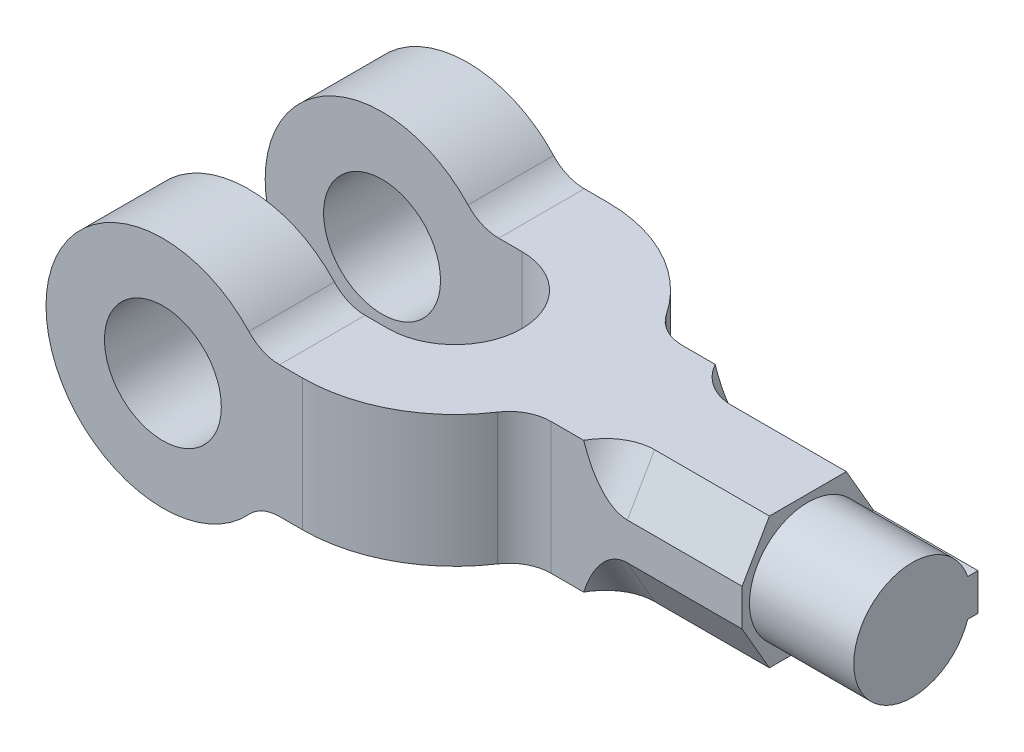
SolidWorks part; units mm, degrees
ref_plane "Front Plane" through (0, 0, 0) normal (0, 0, 1) x (1, 0, 0)
ref_plane "Top Plane" through (0, 0, 0) normal (0, 1, 0) x (1, 0, 0)
ref_plane "Right Plane" through (0, 0, 0) normal (1, 0, 0) x (0, 0, -1)
sketch "Sketch2" plane through (0, 0, 0) normal (0, 0, 1) x (1, 0, 0)
  circle A0 centre (0, 0) radius 28
  circle A1 centre (0, 0) radius 56
  dimension "D1" = 56
  dimension "D2" = 112
extrude "Boss-Extrude1" add sketch "Sketch2" along normal blind 41
ref_plane "Plane1" through (0, 0, -32) normal (0, 0, -1) x (-1, 0, 0)
mirror "Mirror4" about plane through (0, 0, -32) normal (0, 0, -1) of bodies 101
sketch "Sketch3" plane through (0, 0, 0) normal (0, 1, 0) x (1, 0, 0)
  line L0 (-0.029, 112.5865) -> (-0.029, -49887.4135) construction
  line L1 (1.2997, 32) -> (50001.2997, 32) construction
  line L3 (66.971, 32) -> (66.971, 50032) construction
  line L4 (56, 105) -> (-56, 105) construction
  line L5 (66.971, 105) -> (66.971, 64)
  line L6 (66.971, 0) -> (66.971, -41)
  arc A0 (66.971, 0) -> (66.971, 64) centre (66.971, 32) ccw
  arc A1 (66.971, -41) -> (66.971, 105) centre (66.971, 32) ccw
  dimension "D3" = 64
  dimension "D4" = 146
  dimension "D1" = 73
  dimension "D2" = 67
extrude "Boss-Extrude2" add sketch "Sketch3" along normal mid plane 63 separate body
sketch "Sketch4" plane through (66.971, 0, 0) normal (-1, 0, 0) x (0, 0, 1)
  line L0 (0, -31.5) -> (41, -31.5) construction
  line L1 (41, -31.5) -> (41, 31.5) construction
  line L2 (41, 31.5) -> (0, 31.5) construction
  line L3 (0, 31.5) -> (0, -31.5) construction
  line L4 (-105, -31.5) -> (-64, -31.5) construction
  line L5 (-64, -31.5) -> (-64, 31.5) construction
  line L6 (-64, 31.5) -> (-105, 31.5) construction
  line L7 (-105, 31.5) -> (-105, -31.5) construction
  line L8 (0, -31.5) -> (41, -31.5)
  line L9 (41, -31.5) -> (41, 31.5)
  line L10 (41, 31.5) -> (0, 31.5)
  line L11 (0, 31.5) -> (0, -31.5)
  line L12 (-105, -31.5) -> (-64, -31.5)
  line L13 (-64, -31.5) -> (-64, 31.5)
  line L14 (-64, 31.5) -> (-105, 31.5)
  line L15 (-105, 31.5) -> (-105, -31.5)
extrude "Boss-Extrude3" add sketch "Sketch4" along normal up to surface (20.6704 mm away) up to face at (56, 0, -105)
fillet "Fillet1" radius 20 4 edges at (46.3006, -31.5, 20.5) (46.3006, -31.5, -84.5) (46.3006, 31.5, 20.5) (46.3006, 31.5, -84.5)
ref_plane "Plane2" through (236, 0, 0) normal (1, 0, 0) x (0, 0, -1)
sketch "Sketch6" plane through (236, 0, 0) normal (1, 0, 0) x (0, 0, -1)
  line L0 (0, 0) -> (-50000, 0) construction
  line L1 (32, 0) -> (32, 50000) construction
  line L3 (105, 31.5) -> (105, -31.5) construction
  line L4 (105, 31.5) -> (-41, 31.5) construction
  line L5 (63.5, -31.5) -> (0.5, -31.5)
  line L6 (63.5, -31.5) -> (63.5, 31.5)
  line L7 (63.5, 31.5) -> (0.5, 31.5)
  line L8 (0.5, -31.5) -> (0.5, 31.5)
  line L9 (63.5, -31.5) -> (0.5, 31.5) construction
  line L10 (63.5, 31.5) -> (0.5, -31.5) construction
  point P7 (32, 0)
  dimension "D1" = 73
  dimension "D2" = 63
extrude "Boss-Extrude4" add sketch "Sketch6" against normal up to next
fillet "Fillet2" radius 20 2 edges at (132.825, 0, -0.5) (132.825, 0, -63.5)
sketch "Sketch7" plane through (236, 0, 0) normal (1, 0, 0) x (0, 0, -1)
  line L0 (32, -61.6) -> (32, 61.6) construction
  circle A0 centre (32, 0) radius 28
  dimension "D1" = 56
extrude "Boss-Extrude5" add sketch "Sketch7" along normal blind 50
sketch "Sketch8" plane through (236, 0, 0) normal (1, 0, 0) x (0, 0, -1)
  line L1 (68.6181, 0) -> (50.3091, 31.7122)
  line L2 (50.3091, 31.7122) -> (13.6909, 31.7122)
  line L3 (13.6909, 31.7122) -> (-4.6181, 0)
  line L4 (-4.6181, 0) -> (13.6909, -31.7122)
  line L5 (13.6909, -31.7122) -> (50.3091, -31.7122)
  line L6 (50.3091, -31.7122) -> (68.6181, 0)
  circle A0 centre (32, 0) radius 31.7122 construction
  circle A1 centre (32, 0) radius 50
  dimension "D1" = 63.4244
extrude "Cut-Extrude1" cut sketch "Sketch8" against normal blind 80
fillet "Fillet3" radius 25 4 edges at (156, 20.1824, -56.9658) (156, -20.1824, -56.9658) (156, 20.1824, -7.0342) (156, -20.1824, -7.0342)
sketch "Sketch9" plane through (236, 0, 0) normal (1, 0, 0) x (0, 0, -1)
  line L0 (58.5596, 8.8648) -> (63.5, 8.8648)
  line L4 (63.5, -8.8648) -> (63.5, 8.8648)
  line L9 (58.5596, -8.8648) -> (63.5, -8.8648)
  arc A0 (58.5596, -8.8648) -> (58.5596, 8.8648) centre (32, 0) ccw
extrude "Boss-Extrude6" add sketch "Sketch9" along normal up to surface (50 mm away) up to face at (286, 0, -60)
ref_plane "Plane3" through (0, 0, -32) normal (0, 0, 1) x (1, 0, 0)
sketch "Sketch10" plane through (0, 0, -32) normal (0, 0, 1) x (1, 0, 0)
  point P0 (0, 0)
  point P2 (0, 0)
